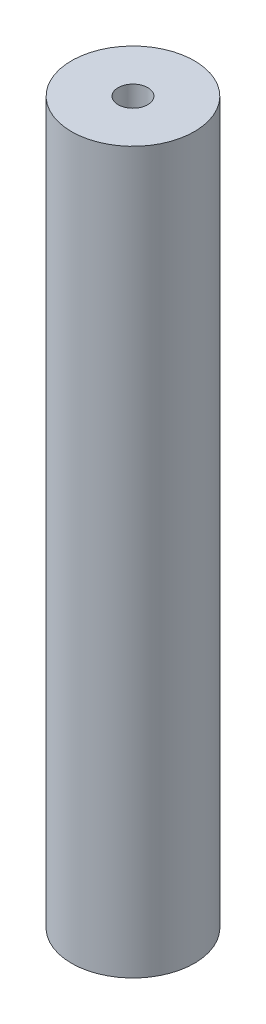
SolidWorks part; units mm, degrees
other "标注1"
sketch "草图3" plane through (-22.25, 4, -10) normal (-0.231, 0.6469, -0.7268) x (-0.9696, -0.2151, 0.1167)
ref_plane "前视基准面" through (0, 0, 0) normal (0, 0, 1) x (1, 0, 0)
ref_plane "上视基准面" through (0, 0, 0) normal (0, 1, 0) x (1, 0, 0)
ref_plane "右视基准面" through (0, 0, 0) normal (1, 0, 0) x (0, 0, -1)
other "Configuration Table"
sketch "草图4" plane through (0, 0, 0) normal (0, 1, 0) x (1, 0, 0)
  circle A0 centre (0, 0) radius 2.9
  circle A1 centre (0, 0) radius 0.7
  dimension "D1" = 5.8
  dimension "D2" = 1.4
extrude "凸台-拉伸1" add sketch "草图4" along normal blind 34 contours A0
extrude "切除-拉伸1" cut sketch "草图4<5>" along normal blind 3 contours A1
sketch "草图4<5>" plane through (0, 0, 0) normal (0, 1, 0) x (1, 0, 0) same geometry as "草图4"
extrude "切除-拉伸2" cut sketch "草图4<6>" against normal blind 3 from surface contours A1 starting at face at (0, 34, 2.9)
sketch "草图4<6>" plane through (0, 0, 0) normal (0, 1, 0) x (1, 0, 0) same geometry as "草图4"
